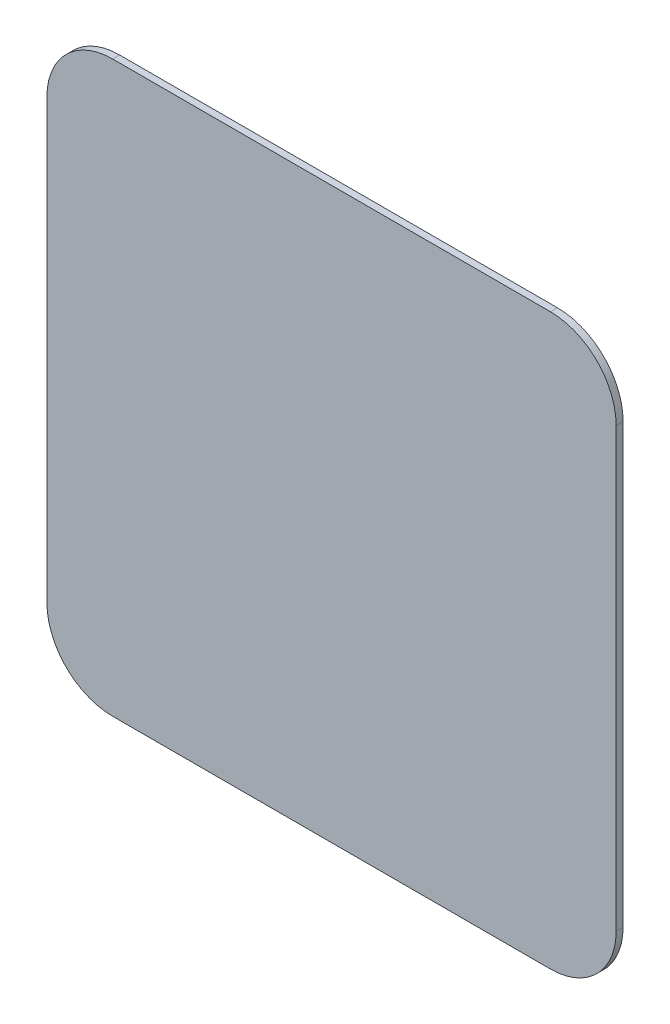
SolidWorks part; units mm, degrees
ref_plane "Front Plane" through (0, 0, 0) normal (0, 0, 1) x (1, 0, 0)
ref_plane "Top Plane" through (0, 0, 0) normal (0, 1, 0) x (1, 0, 0)
ref_plane "Right Plane" through (0, 0, 0) normal (1, 0, 0) x (0, 0, -1)
sketch "Sketch1" plane through (0, 0, 0) normal (0, 0, 1) x (1, 0, 0)
  line L4 (79.7168, 314.2679) -> (-120.2832, 314.2679)
  line L5 (109.7168, 84.2679) -> (109.7168, 284.2679)
  line L6 (-120.2832, 54.2679) -> (79.7168, 54.2679)
  line L7 (-150.2832, 284.2679) -> (-150.2832, 84.2679)
  arc A4 (-120.2832, 314.2679) -> (-150.2832, 284.2679) centre (-120.2832, 284.2679) ccw
  arc A5 (109.7168, 284.2679) -> (79.7168, 314.2679) centre (79.7168, 284.2679) ccw
  arc A6 (79.7168, 54.2679) -> (109.7168, 84.2679) centre (79.7168, 84.2679) ccw
  arc A7 (-150.2832, 84.2679) -> (-120.2832, 54.2679) centre (-120.2832, 84.2679) ccw
extrude "Boss-Extrude1" add sketch "Sketch1" against normal blind 3.175 contours L4 A4 L7 A7 L6 A6 L5 A5
